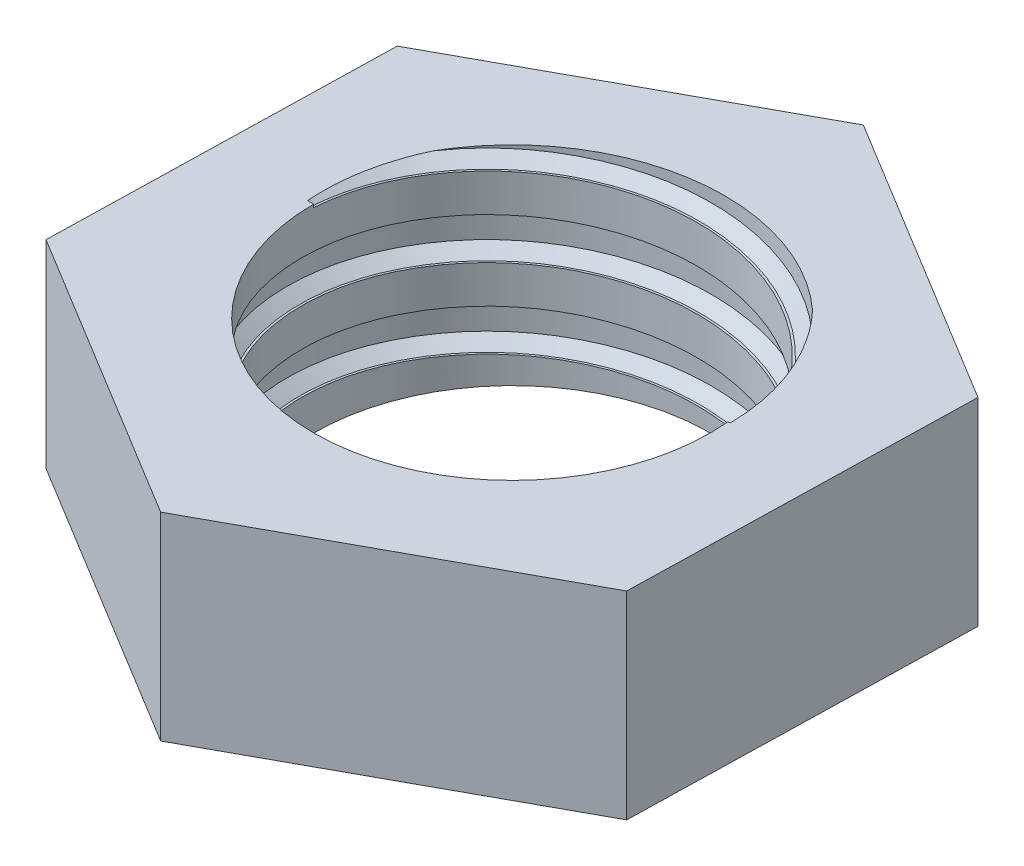
SolidWorks part; units mm, degrees
ref_plane "Front Plane" through (0, 0, 0) normal (0, 0, 1) x (1, 0, 0)
ref_plane "Top Plane" through (0, 0, 0) normal (0, 1, 0) x (1, 0, 0)
ref_plane "Right Plane" through (0, 0, 0) normal (1, 0, 0) x (0, 0, -1)
sketch "Sketch2" plane through (0, 0, 0) normal (0, 1, 0) x (1, 0, 0)
  line L1 (-7.3967, 4.5044) -> (-7.5992, -4.1535)
  line L2 (-7.5992, -4.1535) -> (-0.2026, -8.6579)
  line L3 (-0.2026, -8.6579) -> (7.3967, -4.5044)
  line L4 (7.3967, -4.5044) -> (7.5992, 4.1535)
  line L5 (7.5992, 4.1535) -> (0.2026, 8.6579)
  line L6 (0.2026, 8.6579) -> (-7.3967, 4.5044)
  circle A0 centre (0, 0) radius 7.5 construction
  dimension "D1" = 15
extrude "Boss-Extrude1" add sketch "Sketch2" along normal blind 5
sketch "Sketch3" plane through (0, 5, 0) normal (0, 1, 0) x (1, 0, 0)
  circle A0 centre (0, 0) radius 5
extrude "Cut-Extrude1" cut sketch "Sketch3" against normal blind 5
ref_plane "Plane1" through (0, 6, 0) normal (0, 1, 0) x (1, 0, 0)
sketch "Sketch5" plane through (0, 6, 0) normal (0, 1, 0) x (1, 0, 0)
  circle A0 centre (0, 0) radius 5
curve "Helix/Spiral1" pitch 2 height 58 turns 29
sketch "Sketch6" plane through (0, 0, 0) normal (1, 0, 0) x (0, 0, -1)
  line L0 (-4.9786, 4.4707) -> (-5.056, 4.4707)
  line L1 (-5.056, 4.4707) -> (-5.3663, 4.2348)
  line L2 (-5.3663, 4.2348) -> (-5.3663, 3.6668)
  line L3 (-5.3663, 3.6668) -> (-5.056, 3.4227)
  line L4 (-5.056, 3.4227) -> (-4.9786, 3.4227)
  line L5 (-4.9786, 3.4227) -> (-4.9786, 4.4707)
  spline S0 degree 3 poles (0, 6) (0.6503, 5.9586) (1.9651, 5.8749) (3.6271, 5.75) (4.7398, 5.625) (5.1301, 5.5) (4.7397, 5.375) (3.6276, 5.25) (1.4085, 5.0833) (-1.4084, 4.9167) (-3.6276, 4.75) (-4.7397, 4.625) (-5.1302, 4.5) (-4.7397, 4.375) (-3.6276, 4.25) (-1.4084, 4.0833) (1.4084, 3.9167) (3.6276, 3.75) (4.7397, 3.625) (5.1302, 3.5) (4.7397, 3.375) (3.6276, 3.25) (1.4084, 3.0833) (-1.4084, 2.9167) (-3.6276, 2.75) (-4.7397, 2.625) (-5.1302, 2.5) (-4.7397, 2.375) (-3.6276, 2.25) (-1.4084, 2.0833) (1.4084, 1.9167) (3.6276, 1.75) (4.7397, 1.625) (5.1302, 1.5) (4.7397, 1.375) (3.6276, 1.25) (1.4084, 1.0833) (-1.4084, 0.9167) (-3.6276, 0.75) (-4.7397, 0.625) (-5.1302, 0.5) (-4.7397, 0.375) (-3.6276, 0.25) (-1.4084, 0.0833) (1.4084, -0.0833) (3.6276, -0.25) (4.7397, -0.375) (5.1302, -0.5) (4.7397, -0.625) (3.6276, -0.75) (1.4084, -0.9167) (-1.4084, -1.0833) (-3.6276, -1.25) (-4.7397, -1.375) (-5.1302, -1.5) (-4.7397, -1.625) (-3.6276, -1.75) (-1.4084, -1.9167) (1.4084, -2.0833) (3.6276, -2.25) (4.7397, -2.375) (5.1302, -2.5) (4.7397, -2.625) (3.6276, -2.75) (1.4084, -2.9167) (-1.4084, -3.0833) (-3.6276, -3.25) (-4.7397, -3.375) (-5.1302, -3.5) (-4.7397, -3.625) (-3.6276, -3.75) (-1.4084, -3.9167) (1.4084, -4.0833) (3.6276, -4.25) (4.7397, -4.375) (5.1302, -4.5) (4.7397, -4.625) (3.6276, -4.75) (1.4084, -4.9167) (-1.4084, -5.0833) (-3.6276, -5.25) (-4.7397, -5.375) (-5.1302, -5.5) (-4.7397, -5.625) (-3.6276, -5.75) (-1.4084, -5.9167) (1.4084, -6.0833) (3.6276, -6.25) (4.7397, -6.375) (5.1302, -6.5) (4.7397, -6.625) (3.6276, -6.75) (1.4084, -6.9167) (-1.4084, -7.0833) (-3.6276, -7.25) (-4.7397, -7.375) (-5.1302, -7.5) (-4.7397, -7.625) (-3.6276, -7.75) (-1.4084, -7.9167) (1.4084, -8.0833) (3.6276, -8.25) (4.7397, -8.375) (5.1302, -8.5) (4.7397, -8.625) (3.6276, -8.75) (1.4084, -8.9167) (-1.4084, -9.0833) (-3.6276, -9.25) (-4.7397, -9.375) (-5.1302, -9.5) (-4.7397, -9.625) (-3.6276, -9.75) (-1.4084, -9.9167) (1.4084, -10.0833) (3.6276, -10.25) (4.7397, -10.375) (5.1302, -10.5) (4.7397, -10.625) (3.6276, -10.75) (1.4084, -10.9167) (-1.4084, -11.0833) (-3.6276, -11.25) (-4.7397, -11.375) (-5.1302, -11.5) (-4.7397, -11.625) (-3.6276, -11.75) (-1.4084, -11.9167) (1.4084, -12.0833) (3.6276, -12.25) (4.7397, -12.375) (5.1302, -12.5) (4.7397, -12.625) (3.6276, -12.75) (1.4084, -12.9167) (-1.4084, -13.0833) (-3.6276, -13.25) (-4.7397, -13.375) (-5.1302, -13.5) (-4.7397, -13.625) (-3.6276, -13.75) (-1.4084, -13.9167) (1.4084, -14.0833) (3.6276, -14.25) (4.7397, -14.375) (5.1302, -14.5) (4.7397, -14.625) (3.6276, -14.75) (1.4084, -14.9167) (-1.4084, -15.0833) (-3.6276, -15.25) (-4.7397, -15.375) (-5.1302, -15.5) (-4.7397, -15.625) (-3.6276, -15.75) (-1.4084, -15.9167) (1.4084, -16.0833) (3.6276, -16.25) (4.7397, -16.375) (5.1302, -16.5) (4.7397, -16.625) (3.6276, -16.75) (1.4084, -16.9167) (-1.4084, -17.0833) (-3.6276, -17.25) (-4.7397, -17.375) (-5.1302, -17.5) (-4.7397, -17.625) (-3.6276, -17.75) (-1.4084, -17.9167) (1.4084, -18.0833) (3.6276, -18.25) (4.7397, -18.375) (5.1302, -18.5) (4.7397, -18.625) (3.6276, -18.75) (1.4084, -18.9167) (-1.4084, -19.0833) (-3.6276, -19.25) (-4.7397, -19.375) (-5.1302, -19.5) (-4.7397, -19.625) (-3.6276, -19.75) (-1.4084, -19.9167) (1.4084, -20.0833) (3.6276, -20.25) (4.7397, -20.375) (5.1302, -20.5) (4.7397, -20.625) (3.6276, -20.75) (1.4084, -20.9167) (-1.4084, -21.0833) (-3.6276, -21.25) (-4.7397, -21.375) (-5.1302, -21.5) (-4.7397, -21.625) (-3.6276, -21.75) (-1.4084, -21.9167) (1.4084, -22.0833) (3.6276, -22.25) (4.7397, -22.375) (5.1302, -22.5) (4.7397, -22.625) (3.6276, -22.75) (1.4084, -22.9167) (-1.4084, -23.0833) (-3.6276, -23.25) (-4.7397, -23.375) (-5.1302, -23.5) (-4.7397, -23.625) (-3.6276, -23.75) (-1.4084, -23.9167) (1.4084, -24.0833) (3.6276, -24.25) (4.7397, -24.375) (5.1302, -24.5) (4.7397, -24.625) (3.6276, -24.75) (1.4084, -24.9167) (-1.4084, -25.0833) (-3.6276, -25.25) (-4.7397, -25.375) (-5.1302, -25.5) (-4.7397, -25.625) (-3.6276, -25.75) (-1.4084, -25.9167) (1.4084, -26.0833) (3.6276, -26.25) (4.7397, -26.375) (5.1302, -26.5) (4.7397, -26.625) (3.6276, -26.75) (1.4084, -26.9167) (-1.4084, -27.0833) (-3.6276, -27.25) (-4.7397, -27.375) (-5.1302, -27.5) (-4.7397, -27.625) (-3.6276, -27.75) (-1.4084, -27.9167) (1.4084, -28.0833) (3.6276, -28.25) (4.7397, -28.375) (5.1302, -28.5) (4.7397, -28.625) (3.6276, -28.75) (1.4084, -28.9167) (-1.4084, -29.0833) (-3.6276, -29.25) (-4.7397, -29.375) (-5.1302, -29.5) (-4.7397, -29.625) (-3.6276, -29.75) (-1.4084, -29.9167) (1.4084, -30.0833) (3.6276, -30.25) (4.7397, -30.375) (5.1302, -30.5) (4.7397, -30.625) (3.6276, -30.75) (1.4084, -30.9167) (-1.4084, -31.0833) (-3.6276, -31.25) (-4.7397, -31.375) (-5.1302, -31.5) (-4.7397, -31.625) (-3.6276, -31.75) (-1.4084, -31.9167) (1.4084, -32.0833) (3.6276, -32.25) (4.7397, -32.375) (5.1302, -32.5) (4.7397, -32.625) (3.6276, -32.75) (1.4084, -32.9167) (-1.4084, -33.0833) (-3.6276, -33.25) (-4.7397, -33.375) (-5.1302, -33.5) (-4.7397, -33.625) (-3.6276, -33.75) (-1.4084, -33.9167) (1.4084, -34.0833) (3.6276, -34.25) (4.7397, -34.375) (5.1302, -34.5) (4.7397, -34.625) (3.6276, -34.75) (1.4084, -34.9167) (-1.4084, -35.0833) (-3.6276, -35.25) (-4.7397, -35.375) (-5.1302, -35.5) (-4.7397, -35.625) (-3.6276, -35.75) (-1.4084, -35.9167) (1.4084, -36.0833) (3.6276, -36.25) (4.7397, -36.375) (5.1302, -36.5) (4.7397, -36.625) (3.6276, -36.75) (1.4084, -36.9167) (-1.4084, -37.0833) (-3.6276, -37.25) (-4.7397, -37.375) (-5.1302, -37.5) (-4.7397, -37.625) (-3.6276, -37.75) (-1.4084, -37.9167) (1.4084, -38.0833) (3.6276, -38.25) (4.7397, -38.375) (5.1302, -38.5) (4.7397, -38.625) (3.6276, -38.75) (1.4084, -38.9167) (-1.4084, -39.0833) (-3.6276, -39.25) (-4.7397, -39.375) (-5.1302, -39.5) (-4.7397, -39.625) (-3.6276, -39.75) (-1.4084, -39.9167) (1.4084, -40.0833) (3.6276, -40.25) (4.7397, -40.375) (5.1302, -40.5) (4.7397, -40.625) (3.6276, -40.75) (1.4084, -40.9167) (-1.4084, -41.0833) (-3.6276, -41.25) (-4.7397, -41.375) (-5.1302, -41.5) (-4.7397, -41.625) (-3.6276, -41.75) (-1.4084, -41.9167) (1.4084, -42.0833) (3.6276, -42.25) (4.7397, -42.375) (5.1302, -42.5) (4.7397, -42.625) (3.6276, -42.75) (1.4084, -42.9167) (-1.4084, -43.0833) (-3.6276, -43.25) (-4.7397, -43.375) (-5.1302, -43.5) (-4.7397, -43.625) (-3.6276, -43.75) (-1.4084, -43.9167) (1.4084, -44.0833) (3.6276, -44.25) (4.7397, -44.375) (5.1302, -44.5) (4.7397, -44.625) (3.6276, -44.75) (1.4084, -44.9167) (-1.4084, -45.0833) (-3.6276, -45.25) (-4.7397, -45.375) (-5.1302, -45.5) (-4.7397, -45.625) (-3.6276, -45.75) (-1.4084, -45.9167) (1.4084, -46.0833) (3.6276, -46.25) (4.7397, -46.375) (5.1302, -46.5) (4.7397, -46.625) (3.6276, -46.75) (1.4084, -46.9167) (-1.4084, -47.0833) (-3.6276, -47.25) (-4.7397, -47.375) (-5.1302, -47.5) (-4.7397, -47.625) (-3.6276, -47.75) (-1.4084, -47.9167) (1.4084, -48.0833) (3.6276, -48.25) (4.7397, -48.375) (5.1302, -48.5) (4.7397, -48.625) (3.6276, -48.75) (1.4084, -48.9167) (-1.4084, -49.0833) (-3.6276, -49.25) (-4.7397, -49.375) (-5.1302, -49.5) (-4.7397, -49.625) (-3.6276, -49.75) (-1.4084, -49.9167) (1.4084, -50.0833) (3.6276, -50.25) (4.7397, -50.375) (5.1302, -50.5) (4.7397, -50.625) (3.6276, -50.75) (1.4084, -50.9167) (-1.4085, -51.0833) (-3.6276, -51.25) (-4.7397, -51.375) (-5.1301, -51.5) (-4.7398, -51.625) (-3.6271, -51.75) (-1.9651, -51.8749) (-0.6503, -51.9586) (0, -52) knots 0 0 0 0 0.002155 0.00431 0.006466 0.008621 0.010776 0.012931 0.015086 0.019397 0.021552 0.023707 0.025862 0.028017 0.030172 0.032328 0.036638 0.038793 0.040948 0.043103 0.045259 0.047414 0.049569 0.053879 0.056034 0.05819 0.060345 0.0625 0.064655 0.06681 0.071121 0.073276 0.075431 0.077586 0.079741 0.081897 0.084052 0.088362 0.090517 0.092672 0.094828 0.096983 0.099138 0.101293 0.105603 0.107759 0.109914 0.112069 0.114224 0.116379 0.118534 0.122845 0.125 0.127155 0.12931 0.131466 0.133621 0.135776 0.140086 0.142241 0.144397 0.146552 0.148707 0.150862 0.153017 0.157328 0.159483 0.161638 0.163793 0.165948 0.168103 0.170259 0.174569 0.176724 0.178879 0.181034 0.18319 0.185345 0.1875 0.19181 0.193966 0.196121 0.198276 0.200431 0.202586 0.204741 0.209052 0.211207 0.213362 0.215517 0.217672 0.219828 0.221983 0.226293 0.228448 0.230603 0.232759 0.234914 0.237069 0.239224 0.243534 0.24569 0.247845 0.25 0.252155 0.25431 0.256466 0.260776 0.262931 0.265086 0.267241 0.269397 0.271552 0.273707 0.278017 0.280172 0.282328 0.284483 0.286638 0.288793 0.290948 0.295259 0.297414 0.299569 0.301724 0.303879 0.306034 0.30819 0.3125 0.314655 0.31681 0.318966 0.321121 0.323276 0.325431 0.329741 0.331897 0.334052 0.336207 0.338362 0.340517 0.342672 0.346983 0.349138 0.351293 0.353448 0.355603 0.357759 0.359914 0.364224 0.366379 0.368534 0.37069 0.372845 0.375 0.377155 0.381466 0.383621 0.385776 0.387931 0.390086 0.392241 0.394397 0.398707 0.400862 0.403017 0.405172 0.407328 0.409483 0.411638 0.415948 0.418103 0.420259 0.422414 0.424569 0.426724 0.428879 0.43319 0.435345 0.4375 0.439655 0.44181 0.443966 0.446121 0.450431 0.452586 0.454741 0.456897 0.459052 0.461207 0.463362 0.467672 0.469828 0.471983 0.474138 0.476293 0.478448 0.480603 0.484914 0.487069 0.489224 0.491379 0.493534 0.49569 0.497845 0.502155 0.50431 0.506466 0.508621 0.510776 0.512931 0.515086 0.519397 0.521552 0.523707 0.525862 0.528017 0.530172 0.532328 0.536638 0.538793 0.540948 0.543103 0.545259 0.547414 0.549569 0.553879 0.556034 0.55819 0.560345 0.5625 0.564655 0.56681 0.571121 0.573276 0.575431 0.577586 0.579741 0.581897 0.584052 0.588362 0.590517 0.592672 0.594828 0.596983 0.599138 0.601293 0.605603 0.607759 0.609914 0.612069 0.614224 0.616379 0.618534 0.622845 0.625 0.627155 0.62931 0.631466 0.633621 0.635776 0.640086 0.642241 0.644397 0.646552 0.648707 0.650862 0.653017 0.657328 0.659483 0.661638 0.663793 0.665948 0.668103 0.670259 0.674569 0.676724 0.678879 0.681034 0.68319 0.685345 0.6875 0.69181 0.693966 0.696121 0.698276 0.700431 0.702586 0.704741 0.709052 0.711207 0.713362 0.715517 0.717672 0.719828 0.721983 0.726293 0.728448 0.730603 0.732759 0.734914 0.737069 0.739224 0.743534 0.74569 0.747845 0.75 0.752155 0.75431 0.756466 0.760776 0.762931 0.765086 0.767241 0.769397 0.771552 0.773707 0.778017 0.780172 0.782328 0.784483 0.786638 0.788793 0.790948 0.795259 0.797414 0.799569 0.801724 0.803879 0.806034 0.80819 0.8125 0.814655 0.81681 0.818966 0.821121 0.823276 0.825431 0.829741 0.831897 0.834052 0.836207 0.838362 0.840517 0.842672 0.846983 0.849138 0.851293 0.853448 0.855603 0.857759 0.859914 0.864224 0.866379 0.868534 0.87069 0.872845 0.875 0.877155 0.881466 0.883621 0.885776 0.887931 0.890086 0.892241 0.894397 0.898707 0.900862 0.903017 0.905172 0.907328 0.909483 0.911638 0.915948 0.918103 0.920259 0.922414 0.924569 0.926724 0.928879 0.93319 0.935345 0.9375 0.939655 0.94181 0.943966 0.946121 0.950431 0.952586 0.954741 0.956897 0.959052 0.961207 0.963362 0.967672 0.969828 0.971983 0.974138 0.976293 0.978448 0.980603 0.984914 0.987069 0.989224 0.991379 0.993534 0.99569 0.997845 1 1 1 1 construction
sweep "Cut-Sweep1" cut profiles "Sketch6" path "Helix/Spiral1" align with end faces yes
